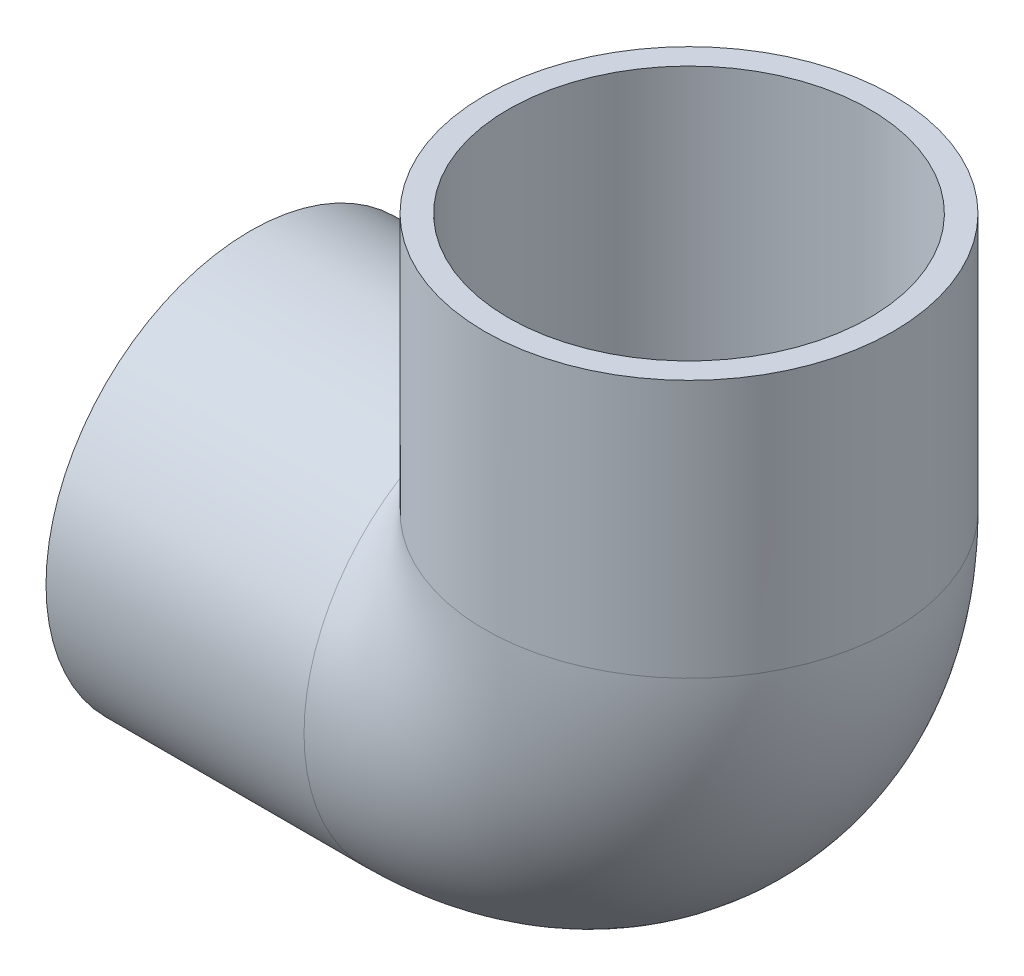
SolidWorks part; units mm, degrees
ref_plane "Front Plane" through (0, 0, 0) normal (0, 0, 1) x (1, 0, 0)
ref_plane "Top Plane" through (0, 0, 0) normal (0, 1, 0) x (1, 0, 0)
ref_plane "Right Plane" through (0, 0, 0) normal (1, 0, 0) x (0, 0, -1)
sketch "Sketch0" plane through (0, 0, 0) normal (0, 0, 1) x (1, 0, 0)
  line L0 (-53.975, 0) -> (0, 0) construction
  line L1 (0, 0) -> (0, 53.975) construction
  line L2 (-22.225, 0) -> (0, 0) construction
  line L3 (0, 0) -> (0, 22.225) construction
  line L4 (-53.975, 25.146) -> (-53.975, -25.146) construction
  line L5 (-22.225, 21.0185) -> (-53.975, 21.209) construction
  line L6 (-22.225, 21.0185) -> (-22.225, -21.0185) construction
  line L7 (-22.225, -21.0185) -> (-53.975, -21.209) construction
  line L8 (-53.975, 21.209) -> (-53.975, -21.209) construction
  line L9 (-25.146, 53.975) -> (25.146, 53.975) construction
  line L10 (-21.209, 53.975) -> (21.209, 53.975) construction
  line L11 (21.209, 53.975) -> (21.0185, 22.225) construction
  line L12 (21.0185, 22.225) -> (-21.0185, 22.225) construction
  line L13 (-21.0185, 22.225) -> (-21.209, 53.975) construction
  line L14 (-22.225, 17.526) -> (-22.225, -17.526) construction
  line L18 (-17.526, 22.225) -> (17.526, 22.225) construction
  dimension "H" = 53.975
  dimension "G" = 22.225
  dimension "M" = 50.292
  dimension "OD A" = 42.418
  dimension "OD B" = 42.037
  dimension "ID" = 35.052
sketch "Sketch1" plane through (0, 0, 0) normal (0, 0, 1) x (1, 0, 0)
  line L0 (-53.975, 0) -> (0, 0) construction
  line L1 (-53.975, 0) -> (0, 0) construction
  line L3 (-53.975, -25.146) -> (-22.225, -25.146)
  line L4 (-53.975, -25.146) -> (-53.975, -21.209)
  line L5 (-53.975, -21.209) -> (-22.225, -21.0185)
  line L6 (-22.225, -25.146) -> (-22.225, -21.0185)
revolve "Revolve1" add sketch "Sketch1" angle 360 about L1
sketch "Sketch2" plane through (0, 0, 0) normal (0, 0, 1) x (1, 0, 0)
  line L0 (21.209, 53.975) -> (21.0185, 22.225)
  line L1 (21.0185, 22.225) -> (25.146, 22.225)
  line L2 (25.146, 22.225) -> (25.146, 53.975)
  line L3 (25.146, 53.975) -> (21.209, 53.975)
  line L4 (0, 0) -> (0, 53.975) construction
  line L5 (0, 0) -> (0, 53.975) construction
revolve "Revolve2" add sketch "Sketch2" angle 360 about L5
sketch "Sketch3" plane through (-22.225, 0, 0) normal (1, 0, 0) x (0, 0, -1)
  circle A0 centre (0, 0) radius 17.526
  circle A1 centre (0, 0) radius 25.146
sketch "Sketch4" plane through (0, 0, 0) normal (0, 0, 1) x (1, 0, 0)
  line L0 (-53.975, 0) -> (0, 0) construction
  line L1 (0, 0) -> (0, 53.975) construction
  line L2 (-53.975, 0) -> (-22.225, 0) construction
  line L3 (0, 22.225) -> (0, 53.975) construction
  arc A0 (-22.225, 0) -> (0, 22.225) centre (-22.225, 22.225) ccw
sweep "Sweep1" add profiles "Sketch3" path "Sketch4"
sketch "Sketch5" plane through (0, 53.975, 0) normal (0, 1, 0) x (1, 0, 0)
  circle A0 centre (0, 0) radius 22.225
  dimension "D1" = 44.45
extrude "Cut-Extrude1" cut sketch "Sketch5" against normal blind 31.75
